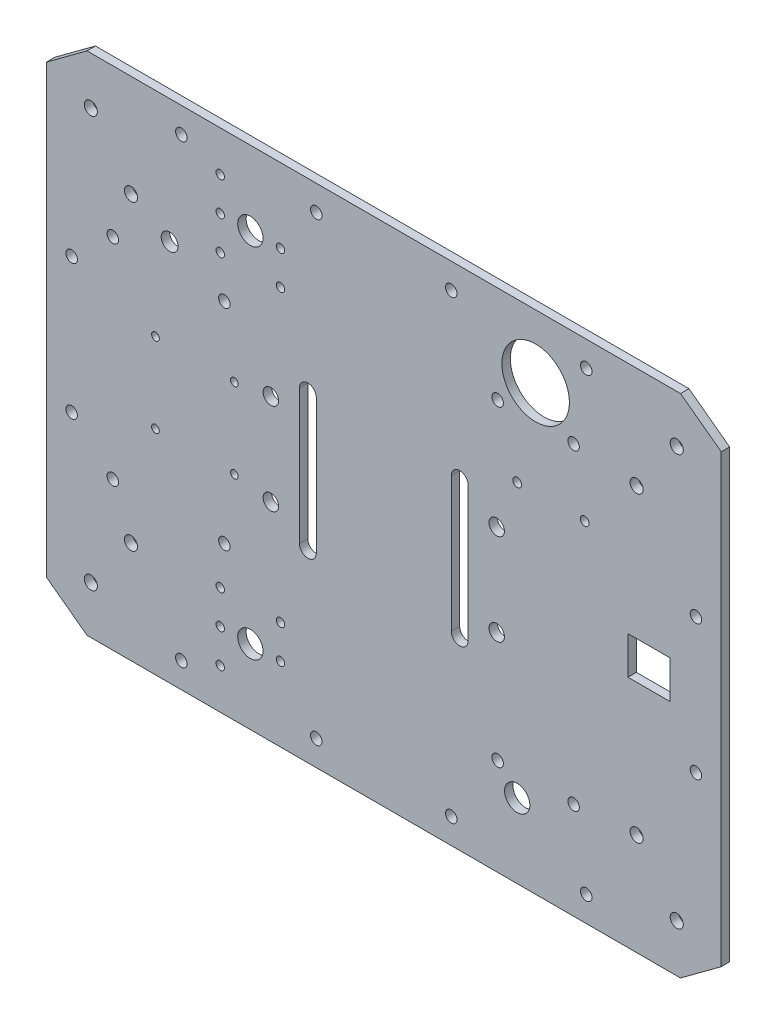
SolidWorks part; units mm, degrees
material "Thornel Mat VMA"
ref_plane "Front Plane" through (0, 0, 0) normal (0, 0, 1) x (1, 0, 0)
ref_plane "Top Plane" through (0, 0, 0) normal (0, 1, 0) x (1, 0, 0)
ref_plane "Right Plane" through (0, 0, 0) normal (1, 0, 0) x (0, 0, -1)
sketch "Sketch1" plane through (0, 0, 0) normal (0, 0, 1) x (1, 0, 0)
  line L0 (-127, 0) -> (127, 0) construction
  line L1 (0, -95.25) -> (0, 95.25) construction
  line L2 (-107.95, 0) -> (-107.95, 41.011) construction
  line L3 (-107.95, 41.011) -> (-95.25, 41.011) construction
  line L4 (-95.25, 41.011) -> (-79.9365, 52.3423) construction
  line L5 (-79.9365, 52.3423) -> (-79.9365, 76.2) construction
  line L6 (-79.9365, 76.2) -> (0, 76.2) construction
  line L7 (-95.25, 41.011) -> (-127, 83.9186) construction
  line L8 (-79.9365, 52.3423) -> (-111.6865, 95.25) construction
  line L9 (-111.6865, -95.25) -> (-127, -83.9186)
  line L10 (111.6865, -95.25) -> (127, -83.9186)
  line L11 (111.6865, 95.25) -> (127, 83.9186)
  line L12 (-87.5933, 46.6767) -> (-95.1475, 56.8856) construction
  line L13 (-95.1475, 56.8856) -> (-110.256, 77.3036) construction
  line L24 (127, -83.9186) -> (127, 83.9186)
  line L26 (111.6865, 95.25) -> (-111.6865, 95.25)
  line L27 (-111.6865, 95.25) -> (-127, 83.9186)
  line L28 (-127, 83.9186) -> (-127, -83.9186)
  line L30 (-111.6865, -95.25) -> (111.6865, -95.25)
  circle A0 centre (-95.1475, 56.8856) radius 2.4638
  circle A1 centre (-110.256, 77.3036) radius 2.4638
  circle A2 centre (110.256, 77.3036) radius 2.4638
  circle A3 centre (95.1475, 56.8856) radius 2.4638
  circle A4 centre (-110.256, -77.3036) radius 2.4638
  circle A5 centre (-95.1475, -56.8856) radius 2.4638
  circle A6 centre (110.256, -77.3036) radius 2.4638
  circle A7 centre (95.1475, -56.8856) radius 2.4638
  point P12 (0, 0)
  point P39 (0, 0)
  dimension "D1" = 190.5
  dimension "D2" = 254
  dimension "D3" = 19.05
  dimension "D4" = 19.05
  dimension "D5" = 12.7
  dimension "D6" = 19.05
  dimension "D7" = 143.5
  dimension "D8" = 12.7
  dimension "D9" = 25.4
extrude "Boss-Extrude1" add sketch "Sketch1" along normal blind 3.175
sketch "Sketch2" plane through (0, 0, 3.175) normal (0, 0, 1) x (1, 0, 0)
  line L0 (-127, 0) -> (127, 0) construction
  line L1 (-127, 83.9186) -> (-127, -83.9186) construction
  line L2 (127, -83.9186) -> (127, 83.9186) construction
  line L3 (57.15, 65.0875) -> (57.15, -65.0875) construction
  line L4 (38.1, 65.0875) -> (76.2, 65.0875)
  line L5 (38.1, 65.0875) -> (38.1, -65.0875)
  line L6 (38.1, -65.0875) -> (76.2, -65.0875)
  line L7 (76.2, 65.0875) -> (76.2, -65.0875)
  line L8 (38.1, 65.0875) -> (76.2, -65.0875) construction
  line L9 (38.1, -65.0875) -> (76.2, 65.0875) construction
  line L10 (57.15, 58.7375) -> (47.625, 58.7375) construction
  line L11 (47.625, 58.7375) -> (38.1, 58.7375) construction
  line L13 (91.8986, -7.112) -> (107.6466, -7.112)
  line L14 (91.8986, -7.112) -> (91.8986, 7.112)
  line L15 (91.8986, 7.112) -> (107.6466, 7.112)
  line L16 (107.6466, -7.112) -> (107.6466, 7.112)
  line L17 (91.8986, -7.112) -> (107.6466, 7.112) construction
  line L18 (91.8986, 7.112) -> (107.6466, -7.112) construction
  circle A0 centre (42.8625, 58.7375) radius 2.159
  circle A1 centre (42.8625, -58.7375) radius 2.159
  circle A2 centre (71.4375, -58.7375) radius 2.159
  circle A3 centre (71.4375, 58.7375) radius 2.159
  point P6 (57.15, 0)
  point P17 (42.8625, 58.7375)
  point P25 (99.7726, 0)
  point P30 (0, 0)
  point P31 (0, 0)
  dimension "D6" = 14.224
  dimension "D1" = 38.1
  dimension "D2" = 130.175
  dimension "D3" = 6.35
  dimension "D4" = 9.525
  dimension "D5" = 69.85
  dimension "D7" = 15.748
extrude "Cut-Extrude1" cut sketch "Sketch2" against normal through all contours A1 | A2 | A3 | A0 | L13 L16 L15 L14 region at (99.7726, 0, 3.175) region at (42.8625, 58.7375, 3.175) region at (42.8625, -58.7375, 3.175) region at (71.4375, -58.7375, 3.175) region at (71.4375, 58.7375, 3.175)
sketch "Sketch3" plane through (0, 0, 3.175) normal (0, 0, 1) x (1, 0, 0)
  line L0 (0, 95.25) -> (0, -95.25) construction
  line L1 (111.6865, 95.25) -> (-111.6865, 95.25) construction
  line L2 (-111.6865, -95.25) -> (111.6865, -95.25) construction
  line L3 (127, 0) -> (-127, 0) construction
  line L4 (127, -83.9186) -> (127, 83.9186) construction
  line L5 (-127, 83.9186) -> (-127, -83.9186) construction
  line L8 (119.3433, -89.5843) -> (111.789, -79.3753) construction
  line L10 (111.6865, -95.25) -> (127, -83.9186) construction
  line L11 (111.6865, -95.25) -> (127, -83.9186)
  circle A0 centre (111.789, -79.3753) radius 1.9844
  circle A1 centre (96.6805, -58.9574) radius 1.9844
  dimension "D2" = 3.9688
  dimension "D3" = 3.9688
  dimension "D1" = 12.7
  dimension "D4" = 25.4
sketch "Sketch5" plane through (0, 0, 0) normal (0, 0, -1) x (-1, 0, 0)
  line L0 (-127, 0) -> (127, 0) construction
  line L1 (105.9946, 43.5) -> (55.9947, 43.5) construction
  line L2 (105.9946, 43.5) -> (105.9946, -43.5) construction
  line L3 (105.9946, -43.5) -> (55.9947, -43.5) construction
  line L4 (55.9947, 43.5) -> (55.9947, -43.5) construction
  line L5 (89.2369, 18.0341) -> (89.2369, -18.0339)
  line L6 (67.8946, 95.25) -> (67.8946, -95.25) construction
  line L7 (-71.4375, 58.7375) -> (-42.8625, 58.7375) construction
  line L8 (0, 64.0679) -> (0, -49.8393) construction
  line L9 (-42.5, 17.2) -> (42.5, 17.2) construction
  line L10 (-42.5, 17.2) -> (-42.5, -17.2) construction
  line L11 (-42.5, -17.2) -> (42.5, -17.2) construction
  line L12 (42.5, 17.2) -> (42.5, -17.2) construction
  line L13 (-42.5, 17.2) -> (42.5, -17.2) construction
  line L14 (-42.5, -17.2) -> (42.5, 17.2) construction
  line L15 (80.5946, 60.96) -> (31.75, 60.96) construction
  line L16 (61.5446, -67.31) -> (-87.4336, -67.31) construction
  line L17 (50.2154, -67.31) -> (50.2154, 67.31) construction
  line L18 (50.2154, 67.31) -> (38.8861, 67.31) construction
  line L19 (-28.575, 25.4) -> (-28.575, -25.4) construction
  line L20 (-111.6865, 95.25) -> (111.6865, 95.25) construction
  line L21 (-127, -83.9186) -> (-127, 83.9186) construction
  line L22 (-57.15, 71.4375) -> (80.5946, 71.4375) construction
  line L23 (80.5946, 71.4375) -> (80.5946, 48.58) construction
  line L25 (80.5946, -77.0458) -> (80.5946, 48.58) construction
  line L26 (127, 0) -> (-127, 0) construction
  line L27 (80.9947, 0) -> (80.9947, -8419.0368) construction
  line L28 (-25.4, 25.4) -> (-25.4, -25.4)
  line L29 (-31.75, 25.4) -> (-31.75, -25.4)
  line L30 (28.575, 25.4) -> (28.575, -25.4) construction
  line L31 (25.4, 25.4) -> (25.4, -25.4)
  line L32 (31.75, 25.4) -> (31.75, -25.4)
  line L33 (71.0787, 0) -> (71.0787, 12.3782) construction
  line L34 (53.2197, 18.0341) -> (89.2369, 18.0341)
  line L35 (53.2197, 18.0341) -> (53.2197, -18.0339)
  line L36 (53.2197, -18.0339) -> (89.2369, -18.0339)
  line L40 (-57.15, 58.7375) -> (-57.15, 95.25) construction
  circle A0 centre (61.5446, -54.61) radius 1.5875
  circle A1 centre (61.5446, -67.31) radius 1.5875
  circle A2 centre (80.5946, 48.58) radius 3.175
  circle A3 centre (-57.15, 71.4375) radius 12.7
  circle A4 centre (61.5446, 54.61) radius 1.5875
  circle A5 centre (61.5446, -80.01) radius 1.5875
  circle A6 centre (-50.2154, -67.31) radius 4.7625
  circle A7 centre (50.2154, -67.31) radius 4.7625
  circle A8 centre (61.5446, 67.31) radius 1.5875
  circle A9 centre (61.5446, 80.01) radius 1.5875
  circle A10 centre (50.2154, 67.31) radius 4.7625
  circle A11 centre (-50.2154, 35.56) radius 1.651
  circle A12 centre (59.9952, 39.4995) radius 2.159
  circle A13 centre (101.9941, 39.4995) radius 2.159
  circle A14 centre (59.9952, -39.4995) radius 2.159
  circle A15 centre (101.9941, -39.4995) radius 2.159
  circle A16 centre (38.8861, 67.31) radius 1.5875
  circle A17 centre (38.8861, 54.61) radius 1.5875
  circle A18 centre (38.8861, -67.31) radius 1.5875
  circle A19 centre (38.8861, -54.61) radius 1.5875
  arc A20 (-25.4, 25.4) -> (-31.75, 25.4) centre (-28.575, 25.4) ccw
  arc A21 (-31.75, -25.4) -> (-25.4, -25.4) centre (-28.575, -25.4) ccw
  arc A22 (25.4, 25.4) -> (31.75, 25.4) centre (28.575, 25.4) cw
  arc A23 (31.75, -25.4) -> (25.4, -25.4) centre (28.575, -25.4) cw
  circle A24 centre (56.2197, 15.0341) radius 1.4478
  circle A25 centre (56.2197, -15.0341) radius 1.4478
  circle A26 centre (85.9377, -15.0341) radius 1.4478
  circle A27 centre (85.9377, 15.0341) radius 1.4478
  circle A28 centre (-42.5, 17.2) radius 2.9083
  circle A29 centre (-42.5, -17.2) radius 2.9083
  circle A30 centre (42.5, -17.2) radius 2.9083
  circle A31 centre (42.5, 17.2) radius 2.9083
  circle A32 centre (-75.6154, 35.6276) radius 1.651
  point P0 (80.9947, 0)
  point P9 (0, 0)
  point P77 (-28.575, 0)
  point P84 (28.575, 0)
  point P89 (71.0787, 0)
  dimension "D10" = 6.35
  dimension "D15" = 2.9997
  dimension "D17" = 3.302
  dimension "D18" = 3.302
  dimension "D25" = 4.0005
  dimension "D45" = 2.8956
  dimension "D9" = 59.69
  dimension "D13" = 14.859
  dimension "D14" = 3
  dimension "D8" = 111.76
  dimension "D1" = 87.0001
  dimension "D2" = 49.9999
  dimension "D4" = 34.4
  dimension "D5" = 85
  dimension "D6" = 6.35
  dimension "D7" = 12.7
  dimension "D11" = 5.08
  dimension "D12" = 25.4
  dimension "D16" = 25.4
  dimension "D26" = 4.0005
  dimension "D38" = 50.8
  dimension "D39" = 6.35
  dimension "D40" = 28.575
  dimension "D41" = 36.0172
  dimension "D42" = 36.068
  dimension "D44" = 3
extrude "Cut-Extrude2" cut sketch "Sketch5" against normal through all contours A3 | A2 | A14 | A15 | A13 | A12 | L29 A21 L28 A20 | A23 L4 A22 L31 | A23 L32 A22 L4 | A27 | A24 | A25 | A26
sketch "Sketch6" plane through (0, 0, 0) normal (0, 0, -1) x (-1, 0, 0)
  line L0 (0, 0) -> (-135.1326, 0) construction
  line L1 (0, 0) -> (0, -95.25) construction
  line L2 (111.6865, -95.25) -> (-111.6865, -95.25) construction
  line L3 (-76.2, -95.25) -> (-76.2, -85.725) construction
  line L4 (117.475, 0) -> (117.475, -25.4) construction
  line L5 (127, 0) -> (-127, 0) construction
  line L6 (127, 83.9186) -> (127, -83.9186) construction
  circle A0 centre (-76.2, -85.725) radius 2.159
  circle A1 centre (-25.4, -85.725) radius 2.159
  circle A2 centre (25.4, -85.725) radius 2.159
  circle A3 centre (76.2, -85.725) radius 2.159
  circle A4 centre (76.2, 85.725) radius 2.159
  circle A5 centre (25.4, 85.725) radius 2.159
  circle A6 centre (-25.4, 85.725) radius 2.159
  circle A7 centre (-76.2, 85.725) radius 2.159
  circle A8 centre (117.475, -25.4) radius 2.159
  circle A9 centre (117.475, 25.4) radius 2.159
  circle A10 centre (-117.475, 25.4) radius 2.159
  circle A11 centre (-117.475, -25.4) radius 2.159
  dimension "D2" = 9.525
  dimension "D3" = 76.2
  dimension "D5" = 9.525
  dimension "D6" = 25.4
  dimension "D4" = 4
extrude "Cut-Extrude3" cut sketch "Sketch6" against normal through all
extrude "Cut-Extrude4" cut sketch "Sketch5<3>" against normal through all contours A28 | A29 | A31 | A30
sketch "Sketch5<3>" plane through (0, 0, 0) normal (0, 0, -1) x (-1, 0, 0) same geometry as "Sketch5"
extrude "Cut-Extrude5" cut sketch "Sketch5<4>" against normal through all contours A10 | A9 | A8 | A4 | A0 | A1 | A5 | A7 | A6
sketch "Sketch5<4>" plane through (0, 0, 0) normal (0, 0, -1) x (-1, 0, 0) same geometry as "Sketch5"
extrude "Cut-Extrude6" cut sketch "Sketch5<5>" against normal blind 2.54 contours A18 | A17 | A16
sketch "Sketch5<5>" plane through (0, 0, 0) normal (0, 0, -1) x (-1, 0, 0) same geometry as "Sketch5"
extrude "Cut-Extrude7" cut sketch "Sketch5<6>" against normal through all contours A17 | A18 | A16
sketch "Sketch5<6>" plane through (0, 0, 0) normal (0, 0, -1) x (-1, 0, 0) same geometry as "Sketch5"
sketch "Sketch8" plane through (0, 0, 3.175) normal (0, 0, 1) x (1, 0, 0)
extrude "Cut-Extrude8" cut sketch "Sketch5<7>" against normal blind 2.54 contours A11
sketch "Sketch5<7>" plane through (0, 0, 0) normal (0, 0, -1) x (-1, 0, 0) same geometry as "Sketch5"
extrude "Cut-Extrude9" cut sketch "Sketch5<9>" against normal blind 2.54 contours A11 | A32
sketch "Sketch5<9>" plane through (0, 0, 0) normal (0, 0, -1) x (-1, 0, 0) same geometry as "Sketch5"
extrude "Cut-Extrude13" cut sketch "Sketch5<12>" against normal through all both and the other way through all contours A11 | A32
sketch "Sketch5<12>" plane through (0, 0, 0) normal (0, 0, -1) x (-1, 0, 0) same geometry as "Sketch5"
extrude "Cut-Extrude14" cut sketch "Sketch5<13>" against normal through all contours A19
sketch "Sketch5<13>" plane through (0, 0, 0) normal (0, 0, -1) x (-1, 0, 0) same geometry as "Sketch5"
